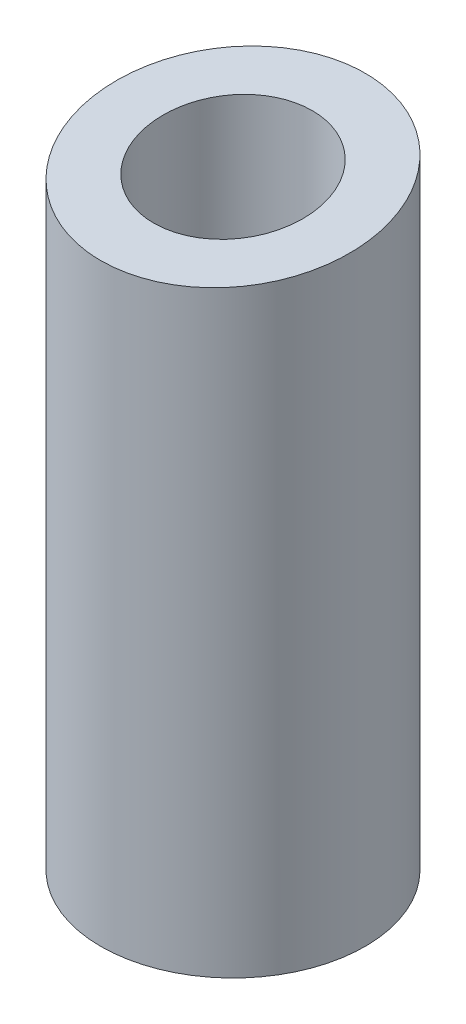
SolidWorks part; units mm, degrees
ref_plane "Front Plane" through (0, 0, 0) normal (0, 0, 1) x (1, 0, 0)
ref_plane "Top Plane" through (0, 0, 0) normal (0, 1, 0) x (1, 0, 0)
ref_plane "Right Plane" through (0, 0, 0) normal (1, 0, 0) x (0, 0, -1)
sketch "Sketch1" plane through (0, 0, 0) normal (0, 1, 0) x (1, 0, 0)
  circle A0 centre (0, 0) radius 2.5
  circle A1 centre (0, 0) radius 1.5
  dimension "D1" = 5
  dimension "D2" = 3
extrude "Boss-Extrude1" add sketch "Sketch1" along normal blind 13
sketch "Sketch2" plane through (0, 13, 0) normal (0, 1, 0) x (1, 0, 0)
  line L0 (0, 2.5) -> (0, -2.5) construction
  circle A0 centre (0, 0) radius 2.5 construction
sketch "Sketch3" plane through (0, 0, 0) normal (0, -1, 0) x (1, 0, 0)
  line L0 (0, 2.5) -> (0, -2.5) construction
ref_plane "Plane1" through (0, 0, 0) normal (1, 0, 0) x (0, 0, -1)
sketch "Sketch4" plane through (0, 0, 0) normal (1, 0, 0) x (0, 0, -1)
  line L0 (-2.5, 0) -> (-2.5, 11.23) construction
  line L1 (-2.5, 0) -> (2.5, 0) construction
  line L2 (-2.5, 13) -> (-2.5, 0) construction
  line L3 (2.5, 11.7992) -> (-2.5, 11.23)
  line L4 (2.5, 0) -> (2.5, 13) construction
  line L5 (-2.5, 11.23) -> (-2.5, 13)
  line L6 (2.5, 13) -> (-2.5, 13) construction
  line L7 (-2.5, 13) -> (2.5, 13)
  line L8 (2.5, 13) -> (2.5, 11.7992)
  dimension "D1" = 11.23
extrude "Cut-Extrude1" cut sketch "Sketch4" against normal blind 13 and the other way blind 13
